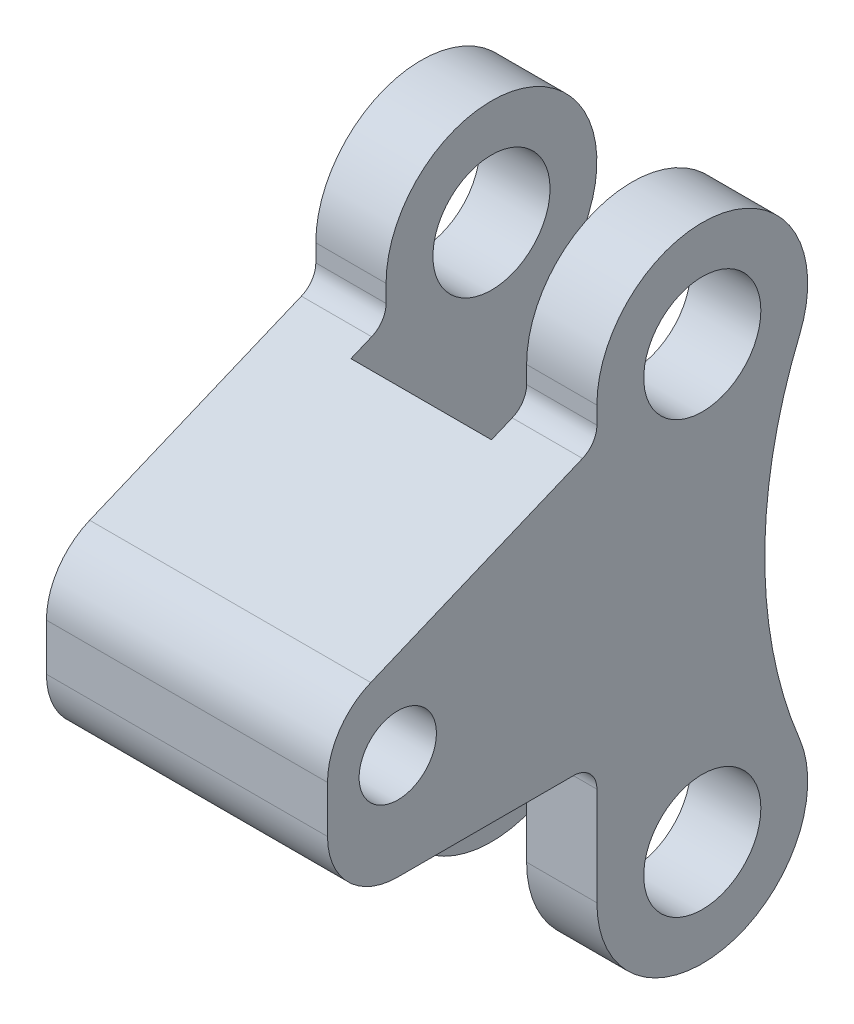
SolidWorks part; units mm, degrees
ref_plane "前基準面" through (0, 0, 0) normal (0, 0, 1) x (1, 0, 0)
ref_plane "上基準面" through (0, 0, 0) normal (0, 1, 0) x (1, 0, 0)
ref_plane "右基準面" through (0, 0, 0) normal (1, 0, 0) x (0, 0, -1)
sketch "草圖1" plane through (0, 0, 0) normal (0, 0, 1) x (1, 0, 0)
  line L0 (0, 0) -> (3, 0)
  line L1 (3, 0) -> (3, 9.7)
  line L2 (3, 9.7) -> (9, 9.7)
  line L3 (9, 9.7) -> (9, 0)
  line L4 (9, 0) -> (12, 0)
  line L5 (12, 0) -> (12, 27.4)
  line L6 (12, 27.4) -> (9, 27.4)
  line L7 (9, 27.4) -> (9, 21.7)
  line L8 (9, 21.7) -> (3, 21.7)
  line L9 (3, 21.7) -> (3, 27.4)
  line L10 (3, 27.4) -> (0, 27.4)
  line L11 (0, 27.4) -> (0, 0)
extrude "填料-伸長1" add sketch "草圖1" along normal blind 22
ref_plane "平面4" through (0, 0, 0) normal (1, 0, 0) x (0, 0, -1)
sketch "草圖2" plane through (0, 0, 0) normal (1, 0, 0) x (0, 0, -1)
  line L0 (-22.7804, 35.9695) -> (-22.7804, -7.5352)
  line L1 (-22.7804, -7.5352) -> (9.2811, -7.5352)
  line L2 (9.2811, -7.5352) -> (9.2811, 35.9695)
  line L3 (9.2811, 35.9695) -> (-22.7804, 35.9695)
  line L4 (-20.5, 9.7) -> (-10, 9.7)
  line L5 (-9, 8.7) -> (-9, 4.5)
  line L6 (-9, 22.9) -> (-9, 21.7)
  line L7 (-9, 21.7) -> (-20.5, 21.7)
  line L8 (-20.5, 21.7) -> (-20.5, 9.7)
  arc A0 (-10, 9.7) -> (-9, 8.7) centre (-10, 8.7) cw
  arc A1 (-9, 4.5) -> (-0.3438, 6.225) centre (-4.5, 4.5) ccw
  arc A2 (-0.3438, 6.225) -> (-0.3438, 21.175) centre (17.6666, 13.7) cw
  arc A3 (-0.3438, 21.175) -> (-9, 22.9) centre (-4.5, 22.9) ccw
  dimension "D1" = 16
  dimension "D2" = 12
extrude "除料-伸長1" cut sketch "草圖2" along normal blind 16
ref_plane "平面5" through (0, 0, 0) normal (0, 1, 0) x (1, 0, 0)
sketch "草圖3" plane through (0, 0, 0) normal (0, 1, 0) x (1, 0, 0)
  line L0 (3, -0.163) -> (3, -10.5)
  line L1 (3, -10.5) -> (9, -10.5)
  line L2 (9, -10.5) -> (9, -0.163)
  line L3 (9, -0.163) -> (3, -0.163)
  line L4 (6, -15) -> (6, -0.163) construction
  line L6 (9, -0.163) -> (3, -0.163) construction
  line L8 (12, -20.5) -> (0, -20.5) construction
  dimension "D1" = 10
extrude "除料-伸長2" cut sketch "草圖3" along normal blind 30
ref_plane "平面6" through (0, 0, 4.5) normal (0, 0, 1) x (1, 0, 0)
ref_plane "平面7" through (6, 0, 0) normal (1, 0, 0) x (0, 0, -1)
sketch "草圖9" plane through (12, 0, 0) normal (1, 0, 0) x (0, 0, -1)
  circle A0 centre (-4.5, 4.5) radius 2.5
  circle A1 centre (-4.5, 22.9) radius 2.5
  dimension "D1" = 5
  dimension "D2" = 5
extrude "除料-伸長4" cut sketch "草圖9" against normal through all
hole_wizard "M4 螺紋孔1" positions "草圖11" profile "草圖10" tap size "M4" standard "Gb" end condition through all
sketch "草圖11" plane through (12, 0, 0) normal (1, 0, 0) x (0, 0, -1)
  line L3 (-20.5, 21.7) -> (-20.5, 9.7) construction
  line L4 (-20.5, 9.7) -> (-10, 9.7) construction
  point P0 (-17.5, 14.2)
  dimension "D1" = 3
  dimension "D2" = 4.5
cosmetic thread "鑽孔螺紋1" parameters "D2"=4
sketch "草圖10" plane through (12, 14.2, 17.5) normal (0, 1, 0) x (0, 0, -1)
  line L0 (0, 0) -> (0, 12)
  line L1 (0, 12) -> (1.65, 12)
  line L2 (1.65, 12) -> (1.65, 0)
  line L5 (1.65, 0) -> (0, 0)
  line L11 (0, -6.35) -> (0, 107.95) construction
  dimension "貫穿螺孔鑽直徑" = 3.3
  dimension "貫穿螺孔鑽深度" = 12
chamfer "導角1" distance 12 distance2 5 1 edges at (6, 21.7, 20.5) first distance on face at (6, 21.7, 12.25)
fillet "圓角2" radius 3 1 edges at (6, 9.7, 20.5)
fillet "圓角3" radius 3 1 edges at (6, 16.7, 20.5)
fillet "圓角4" radius 1 2 edges at (10.5, 21.4917, 9) (1.5, 21.4917, 9)
